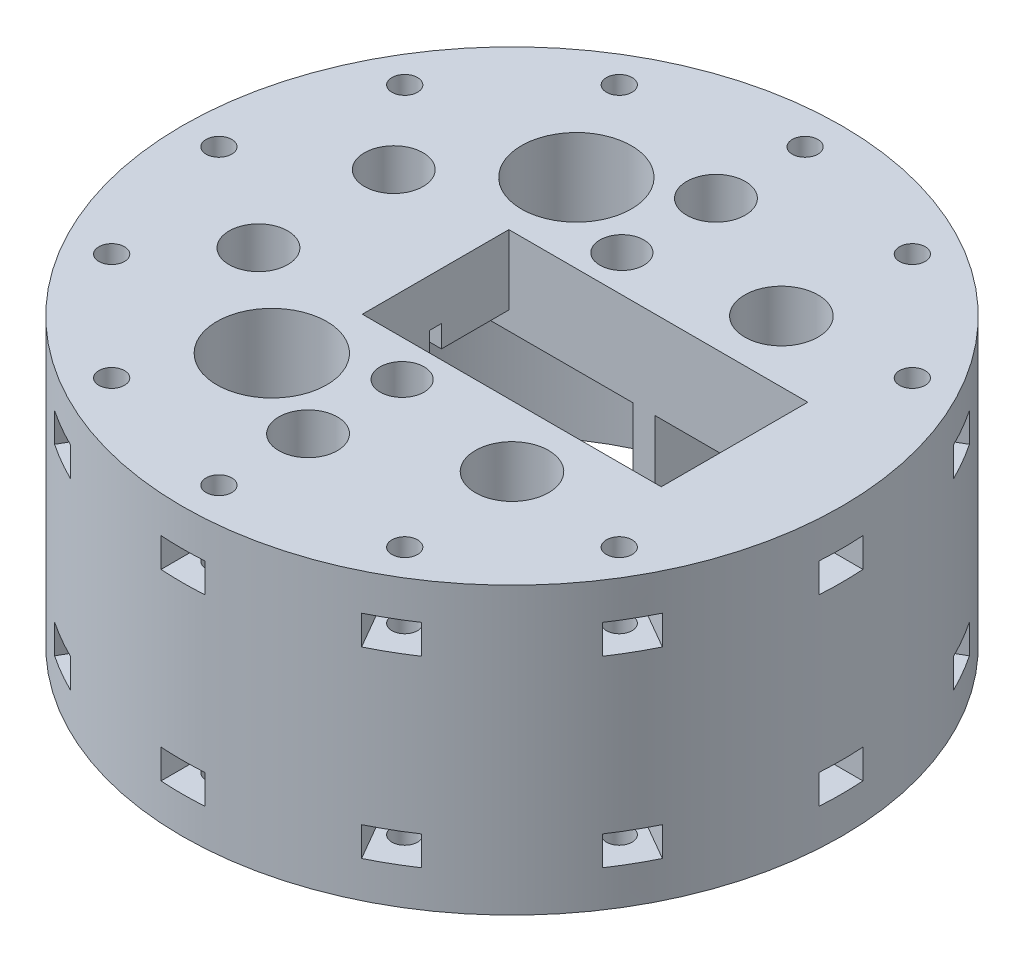
SolidWorks part; units mm, degrees
ref_plane "Front Plane" through (0, 0, 0) normal (0, 0, 1) x (1, 0, 0)
ref_plane "Top Plane" through (0, 0, 0) normal (0, 1, 0) x (1, 0, 0)
ref_plane "Right Plane" through (0, 0, 0) normal (1, 0, 0) x (0, 0, -1)
sketch "Sketch1" plane through (0, 0, 0) normal (0, 1, 0) x (1, 0, 0)
  line L0 (-43.0464, 0) -> (41.9462, 0) construction
  line L1 (0, 43.1152) -> (0, -41.8775) construction
  circle A1 centre (0, 0) radius 45
  dimension "D2" = 90
extrude "Boss-Extrude1" add sketch "Sketch1" along normal blind 39
sketch "Sketch2" plane through (0, 0, 0) normal (0, -1, 0) x (1, 0, 0)
  circle A0 centre (0, 0) radius 35
  dimension "D1" = 70
extrude "Cut-Extrude1" cut sketch "Sketch2" against normal blind 27
sketch "Sketch3" plane through (0, 27, 0) normal (0, -1, 0) x (1, 0, 0)
  line L0 (35, 0) -> (-35, 0) construction
  line L1 (0, -35) -> (0, 35) construction
  line L3 (37.5324, -10) -> (-17.4676, -10)
  line L4 (37.5324, -10) -> (37.5324, 10)
  line L5 (37.5324, 10) -> (-17.4676, 10)
  line L6 (-17.4676, -10) -> (-17.4676, 10)
  circle A0 centre (0, 0) radius 35 construction
  circle A1 centre (0, 0) radius 35 construction
  dimension "D1" = 20
  dimension "D2" = 55
  dimension "D3" = 10
  dimension "D4" = 37.5324
extrude "Cut-Extrude2" cut sketch "Sketch3" against normal blind 2.5 and the other way up to next
sketch "Sketch4" plane through (0, 29.5, 0) normal (0, -1, 0) x (1, 0, 0)
  line L0 (37.5324, 0) -> (-17.4676, 0) construction
  line L1 (37.5324, 10) -> (37.5324, -10) construction
  line L2 (-17.4676, 10) -> (-17.4676, -10) construction
  line L3 (0, -10) -> (0, 10) construction
  line L4 (-17.4676, -10) -> (33.541, -10) construction
  line L5 (33.541, 10) -> (-17.4676, 10) construction
  line L7 (30.3722, -10) -> (-10.4278, -10)
  line L8 (30.3722, -10) -> (30.3722, 10)
  line L9 (30.3722, 10) -> (-10.4278, 10)
  line L10 (-10.4278, -10) -> (-10.4278, 10)
  dimension "D1" = 20
  dimension "D2" = 40.8
  dimension "D3" = 30.3722
  dimension "D4" = 10
extrude "Cut-Extrude3" cut sketch "Sketch4" against normal blind 10.5
sketch "Sketch8" plane through (0, 27, 0) normal (0, -1, 0) x (1, 0, 0)
  line L0 (-17.4676, 0) -> (-35, 0) construction
  line L1 (-17.4676, 10) -> (-17.4676, -10) construction
  line L2 (8.0367, 10) -> (8.0367, 34.0648) construction
  line L3 (33.541, 10) -> (-17.4676, 10) construction
  line L4 (8.0367, -10) -> (8.0367, -29.3194) construction
  line L5 (-17.4676, -10) -> (33.541, -10) construction
  line L6 (6.5367, 10) -> (6.5367, 34.3842)
  line L7 (9.5367, 10) -> (9.5367, 33.6757)
  line L8 (9.5367, 10) -> (6.5367, 10)
  line L9 (9.5367, -10) -> (6.5367, -10)
  line L10 (6.5367, -10) -> (6.5367, -34.3842)
  line L11 (9.5367, -10) -> (9.5367, -33.6757)
  line L12 (-17.4676, 1.5) -> (-34.9678, 1.5)
  line L13 (-17.4676, -1.5) -> (-34.9678, -1.5)
  line L14 (-17.4676, 1.5) -> (-17.4676, -1.5)
  arc A0 (33.541, 10) -> (33.541, -10) centre (0, 0) ccw construction
  arc A1 (9.5367, 33.6757) -> (6.5367, 34.3842) centre (7.9531, 33.6757) ccw
  arc A2 (9.5367, -33.6757) -> (6.5367, -34.3842) centre (7.9531, -33.6757) cw
  arc A3 (-34.9678, 1.5) -> (-34.9678, -1.5) centre (-34.9678, 0) ccw
  dimension "D3" = 1.5
  dimension "D1" = 1.5
  dimension "D2" = 1.5
  dimension "D4" = 1.5
extrude "Boss-Extrude2" add sketch "Sketch8" along normal through all
sketch "Sketch13" plane through (0, 27, 0) normal (0, -1, 0) x (1, 0, 0)
  line L0 (0, 0) -> (0, 35) construction
  line L1 (0, 0) -> (-17.5, 30.3109) construction
  line L2 (0, 0) -> (-41.2446, 0) construction
  line L3 (-32.8892, 11.9707) -> (0, 0) construction
  line L5 (0, 0) -> (24.7487, 24.7487) construction
  arc A0 (6.5367, 34.3842) -> (-34.9678, 1.5) centre (0, 0) ccw construction
  circle A1 centre (-12, 20.7846) radius 7.5
  circle A2 centre (-25.3717, 9.2345) radius 4
  arc A3 (33.541, 10) -> (9.5367, 33.6757) centre (0, 0) ccw construction
  circle A4 centre (18.3848, 18.3848) radius 5
  circle A5 centre (18.3848, -18.3848) radius 5
  circle A6 centre (-12, -20.7846) radius 7.5
  circle A7 centre (-25.3717, -9.2345) radius 4
  circle A8 centre (0, -15) radius 3
  circle A9 centre (0, -27.8351) radius 4
  circle A10 centre (0, 27.8351) radius 4
  circle A11 centre (0, 15) radius 3
  dimension "D3" = 15
  dimension "D6" = 8
  dimension "D8" = 10
  dimension "D10" = 8
  dimension "D11" = 6
  dimension "D1" = 30
  dimension "D2" = 20
  dimension "D4" = 27
  dimension "D5" = 24
  dimension "D7" = 45
  dimension "D9" = 26
  dimension "D12" = 15
extrude "Cut-Extrude7" cut sketch "Sketch13" against normal through all
sketch "Sketch15" plane through (0, 0, -1.5) normal (0, 0, -1) x (-1, 0, 0)
  line L0 (34.9678, 0) -> (17.4676, 27)
  line L1 (17.4676, 27) -> (17.4676, 0)
  line L3 (17.4676, 0) -> (34.9678, 0)
extrude "Cut-Extrude8" cut sketch "Sketch15" against normal blind 3
sketch "Sketch16" plane through (0, 29.5, 0) normal (0, -1, 0) x (1, 0, 0)
  line L0 (-17.4676, 0) -> (37.5324, 0) construction
  line L1 (-17.4676, 10) -> (-17.4676, -10) construction
  line L2 (37.5324, -10) -> (37.5324, 10) construction
  line L3 (30.3722, -0.8) -> (37.5324, -0.8)
  line L4 (-10.4278, -0.8) -> (-17.4676, -0.8)
  line L5 (-10.4278, 10) -> (-10.4278, -10) construction
  line L6 (-10.4278, 0.8) -> (-17.4676, 0.8)
  line L7 (-17.4676, 0.8) -> (-17.4676, -0.8)
  line L8 (-10.4278, 0.8) -> (-10.4278, -0.8)
  line L9 (30.3722, -10) -> (30.3722, 10) construction
  line L10 (30.3722, 0.8) -> (37.5324, 0.8)
  line L11 (37.5324, 0.8) -> (37.5324, -0.8)
  line L12 (30.3722, 0.8) -> (30.3722, -0.8)
  dimension "D1" = 0.8
extrude "Cut-Extrude10" cut sketch "Sketch16" against normal blind 3
sketch "Sketch27" plane through (0, 0, 0) normal (0, -1, 0) x (1, 0, 0)
  line L0 (0, 0) -> (0, -53.17) construction
  line L1 (0, 0) -> (47.7582, -27.5732) construction
  line L3 (31.641, -18.2679) -> (31.641, -21.7321) construction
  line L4 (31.641, -21.7321) -> (34.641, -23.4641) construction
  line L5 (34.641, -23.4641) -> (37.641, -21.7321) construction
  line L6 (37.641, -21.7321) -> (37.641, -18.2679) construction
  line L7 (37.641, -18.2679) -> (34.641, -16.5359) construction
  line L8 (34.641, -16.5359) -> (31.641, -18.2679) construction
  circle A0 centre (0, 0) radius 40 construction
  circle A1 centre (34.641, -20) radius 1.75
  circle A2 centre (0, 0) radius 35 construction
  circle A3 centre (34.641, -20) radius 3 construction
  circle A4 centre (20, -34.641) radius 1.75
  circle A5 centre (0, -40) radius 1.75
  circle A6 centre (-20, -34.641) radius 1.75
  circle A7 centre (-34.641, -20) radius 1.75
  circle A8 centre (-40, 0) radius 1.75
  circle A9 centre (-34.641, 20) radius 1.75
  circle A10 centre (-20, 34.641) radius 1.75
  circle A11 centre (0, 40) radius 1.75
  circle A12 centre (20, 34.641) radius 1.75
  circle A13 centre (34.641, 20) radius 1.75
  circle A15 centre (40, 0) radius 1.75 [skipped]
  point P28 (0, 0)
  point P41 (0, 0)
  dimension "D1" = 80
  dimension "D3" = 3.5
  dimension "D4" = 70
  dimension "D5" = 6
  dimension "D6" = 12
  dimension "D2" = 60
extrude "Cut-Extrude15" cut sketch "Sketch27" against normal through all
ref_plane "Plane1" through (0, 34, 0) normal (0, 1, 0) x (1, 0, 0)
sketch "Sketch28" plane through (0, 34, 0) normal (0, 1, 0) x (1, 0, 0)
  line L0 (0, 0) -> (-54.493, 0) construction
  line L1 (-31.641, 18.2679) -> (-31.641, 21.7321)
  line L2 (-36.5359, 0) -> (-38.2679, 3)
  line L3 (-38.2679, 3) -> (-44.8999, 3)
  line L4 (-31.641, 21.7321) -> (-37.3844, 25.048)
  line L5 (-40.3844, 19.8519) -> (-34.641, 16.5359)
  line L6 (-44.8999, -3) -> (-38.2679, -3)
  line L7 (-38.2679, -3) -> (-36.5359, 0)
  line L8 (-43.4641, 0) -> (-42.5981, -1.5) [skipped]
  line L9 (-41.7321, 3) -> (-42.5981, 1.5) [skipped]
  line L10 (-34.641, 16.5359) -> (-31.641, 18.2679)
  line L11 (-18.2679, 31.641) -> (-16.5359, 34.641)
  line L12 (-16.5359, 34.641) -> (-19.8519, 40.3844)
  line L13 (-25.048, 37.3844) -> (-21.7321, 31.641)
  line L14 (-21.7321, 31.641) -> (-18.2679, 31.641)
  line L15 (0, 36.5359) -> (3, 38.2679)
  line L16 (3, 38.2679) -> (3, 44.8999)
  line L17 (-3, 44.8999) -> (-3, 38.2679)
  line L18 (-3, 38.2679) -> (0, 36.5359)
  line L19 (18.2679, 31.641) -> (21.7321, 31.641)
  line L20 (21.7321, 31.641) -> (25.048, 37.3844)
  line L21 (19.8519, 40.3844) -> (16.5359, 34.641)
  line L22 (16.5359, 34.641) -> (18.2679, 31.641)
  line L23 (31.641, 18.2679) -> (34.641, 16.5359)
  line L24 (34.641, 16.5359) -> (40.3844, 19.8519)
  line L25 (37.3844, 25.048) -> (31.641, 21.7321)
  line L26 (31.641, 21.7321) -> (31.641, 18.2679)
  line L27 (36.5359, 0) -> (38.2679, -3)
  line L28 (38.2679, -3) -> (44.8999, -3)
  line L29 (44.8999, 3) -> (38.2679, 3)
  line L30 (38.2679, 3) -> (36.5359, 0)
  line L31 (31.641, -18.2679) -> (31.641, -21.7321)
  line L32 (31.641, -21.7321) -> (37.3844, -25.048)
  line L33 (40.3844, -19.8519) -> (34.641, -16.5359)
  line L34 (34.641, -16.5359) -> (31.641, -18.2679)
  line L35 (18.2679, -31.641) -> (16.5359, -34.641)
  line L36 (16.5359, -34.641) -> (19.8519, -40.3844)
  line L37 (25.048, -37.3844) -> (21.7321, -31.641)
  line L38 (21.7321, -31.641) -> (18.2679, -31.641)
  line L39 (0, -36.5359) -> (-3, -38.2679)
  line L40 (-3, -38.2679) -> (-3, -44.8999)
  line L41 (3, -44.8999) -> (3, -38.2679)
  line L42 (3, -38.2679) -> (0, -36.5359)
  line L43 (-18.2679, -31.641) -> (-21.7321, -31.641)
  line L44 (-21.7321, -31.641) -> (-25.048, -37.3844)
  line L45 (-19.8519, -40.3844) -> (-16.5359, -34.641)
  line L46 (-16.5359, -34.641) -> (-18.2679, -31.641)
  line L47 (-31.641, -18.2679) -> (-34.641, -16.5359)
  line L48 (-34.641, -16.5359) -> (-40.3844, -19.8519)
  line L49 (-37.3844, -25.048) -> (-31.641, -21.7321)
  line L50 (-31.641, -21.7321) -> (-31.641, -18.2679)
  arc A0 (-44.8999, 3) -> (-44.8999, -3) centre (0, 0) ccw
  circle A1 centre (-40, 0) radius 3 construction
  arc A2 (-37.3844, 25.048) -> (-40.3844, 19.8519) centre (0, 0) ccw
  circle A3 centre (-34.641, 20) radius 3 construction
  arc A4 (-19.8519, 40.3844) -> (-25.048, 37.3844) centre (0, 0) ccw
  circle A5 centre (-20, 34.641) radius 3 construction
  arc A6 (3, 44.8999) -> (-3, 44.8999) centre (0, 0) ccw
  circle A7 centre (0, 40) radius 3 construction
  arc A8 (25.048, 37.3844) -> (19.8519, 40.3844) centre (0, 0) ccw
  circle A9 centre (20, 34.641) radius 3 construction
  arc A10 (40.3844, 19.8519) -> (37.3844, 25.048) centre (0, 0) ccw
  circle A11 centre (34.641, 20) radius 3 construction
  arc A12 (44.8999, -3) -> (44.8999, 3) centre (0, 0) ccw
  circle A13 centre (40, 0) radius 3 construction
  arc A14 (37.3844, -25.048) -> (40.3844, -19.8519) centre (0, 0) ccw
  circle A15 centre (34.641, -20) radius 3 construction
  arc A16 (19.8519, -40.3844) -> (25.048, -37.3844) centre (0, 0) ccw
  circle A17 centre (20, -34.641) radius 3 construction
  arc A18 (-3, -44.8999) -> (3, -44.8999) centre (0, 0) ccw
  circle A19 centre (0, -40) radius 3 construction
  arc A20 (-25.048, -37.3844) -> (-19.8519, -40.3844) centre (0, 0) ccw
  circle A21 centre (-20, -34.641) radius 3 construction
  arc A22 (-40.3844, -19.8519) -> (-37.3844, -25.048) centre (0, 0) ccw
  circle A23 centre (-34.641, -20) radius 3 construction
  point P94 (0, 0)
  dimension "D1" = 90
  dimension "D2" = 6
  dimension "D3" = 12
extrude "Cut-Extrude17" cut sketch "Sketch28" against normal blind 4
ref_plane "Plane2" through (0, 5, 0) normal (0, -1, 0) x (-1, 0, 0)
sketch "Sketch30" plane through (0, 5, 0) normal (0, -1, 0) x (-1, 0, 0)
  line L0 (0, 0) -> (56.1913, 0) construction
  line L1 (31.641, -18.2679) -> (31.641, -21.7321)
  line L2 (36.5359, 0) -> (38.2679, -3)
  line L3 (38.2679, -3) -> (44.8999, -3)
  line L4 (31.641, -21.7321) -> (37.3844, -25.048)
  line L5 (40.3844, -19.8519) -> (34.641, -16.5359)
  line L6 (44.8999, 3) -> (38.2679, 3)
  line L7 (38.2679, 3) -> (36.5359, 0)
  line L8 (43.4641, 0) -> (42.5981, 1.5) [skipped]
  line L9 (41.7321, -3) -> (42.5981, -1.5) [skipped]
  line L10 (34.641, -16.5359) -> (31.641, -18.2679)
  line L11 (18.2679, -31.641) -> (16.5359, -34.641)
  line L12 (16.5359, -34.641) -> (19.8519, -40.3844)
  line L13 (25.048, -37.3844) -> (21.7321, -31.641)
  line L14 (21.7321, -31.641) -> (18.2679, -31.641)
  line L15 (0, -36.5359) -> (-3, -38.2679)
  line L16 (-3, -38.2679) -> (-3, -44.8999)
  line L17 (3, -44.8999) -> (3, -38.2679)
  line L18 (3, -38.2679) -> (0, -36.5359)
  line L19 (-18.2679, -31.641) -> (-21.7321, -31.641)
  line L20 (-21.7321, -31.641) -> (-25.048, -37.3844)
  line L21 (-19.8519, -40.3844) -> (-16.5359, -34.641)
  line L22 (-16.5359, -34.641) -> (-18.2679, -31.641)
  line L23 (-31.641, -18.2679) -> (-34.641, -16.5359)
  line L24 (-34.641, -16.5359) -> (-40.3844, -19.8519)
  line L25 (-37.3844, -25.048) -> (-31.641, -21.7321)
  line L26 (-31.641, -21.7321) -> (-31.641, -18.2679)
  line L27 (-36.5359, 0) -> (-38.2679, 3)
  line L28 (-38.2679, 3) -> (-44.8999, 3)
  line L29 (-44.8999, -3) -> (-38.2679, -3)
  line L30 (-38.2679, -3) -> (-36.5359, 0)
  line L31 (-31.641, 18.2679) -> (-31.641, 21.7321)
  line L32 (-31.641, 21.7321) -> (-37.3844, 25.048)
  line L33 (-40.3844, 19.8519) -> (-34.641, 16.5359)
  line L34 (-34.641, 16.5359) -> (-31.641, 18.2679)
  line L35 (-18.2679, 31.641) -> (-16.5359, 34.641)
  line L36 (-16.5359, 34.641) -> (-19.8519, 40.3844)
  line L37 (-25.048, 37.3844) -> (-21.7321, 31.641)
  line L38 (-21.7321, 31.641) -> (-18.2679, 31.641)
  line L39 (0, 36.5359) -> (3, 38.2679)
  line L40 (3, 38.2679) -> (3, 44.8999)
  line L41 (-3, 44.8999) -> (-3, 38.2679)
  line L42 (-3, 38.2679) -> (0, 36.5359)
  line L43 (18.2679, 31.641) -> (21.7321, 31.641)
  line L44 (21.7321, 31.641) -> (25.048, 37.3844)
  line L45 (19.8519, 40.3844) -> (16.5359, 34.641)
  line L46 (16.5359, 34.641) -> (18.2679, 31.641)
  line L47 (31.641, 18.2679) -> (34.641, 16.5359)
  line L48 (34.641, 16.5359) -> (40.3844, 19.8519)
  line L49 (37.3844, 25.048) -> (31.641, 21.7321)
  line L50 (31.641, 21.7321) -> (31.641, 18.2679)
  arc A0 (44.8999, -3) -> (44.8999, 3) centre (0, 0) ccw
  circle A1 centre (40, 0) radius 3 construction
  arc A2 (37.3844, -25.048) -> (40.3844, -19.8519) centre (0, 0) ccw
  circle A3 centre (34.641, -20) radius 3 construction
  arc A4 (19.8519, -40.3844) -> (25.048, -37.3844) centre (0, 0) ccw
  circle A5 centre (20, -34.641) radius 3 construction
  arc A6 (-3, -44.8999) -> (3, -44.8999) centre (0, 0) ccw
  circle A7 centre (0, -40) radius 3 construction
  arc A8 (-25.048, -37.3844) -> (-19.8519, -40.3844) centre (0, 0) ccw
  circle A9 centre (-20, -34.641) radius 3 construction
  arc A10 (-40.3844, -19.8519) -> (-37.3844, -25.048) centre (0, 0) ccw
  circle A11 centre (-34.641, -20) radius 3 construction
  arc A12 (-44.8999, 3) -> (-44.8999, -3) centre (0, 0) ccw
  circle A13 centre (-40, 0) radius 3 construction
  arc A14 (-37.3844, 25.048) -> (-40.3844, 19.8519) centre (0, 0) ccw
  circle A15 centre (-34.641, 20) radius 3 construction
  arc A16 (-19.8519, 40.3844) -> (-25.048, 37.3844) centre (0, 0) ccw
  circle A17 centre (-20, 34.641) radius 3 construction
  arc A18 (3, 44.8999) -> (-3, 44.8999) centre (0, 0) ccw
  circle A19 centre (0, 40) radius 3 construction
  arc A20 (25.048, 37.3844) -> (19.8519, 40.3844) centre (0, 0) ccw
  circle A21 centre (20, 34.641) radius 3 construction
  arc A22 (40.3844, 19.8519) -> (37.3844, 25.048) centre (0, 0) ccw
  circle A23 centre (34.641, 20) radius 3 construction
  point P94 (0, 0)
  dimension "D1" = 90
  dimension "D2" = 6
  dimension "D3" = 12
extrude "Cut-Extrude19" cut sketch "Sketch30" against normal blind 4
